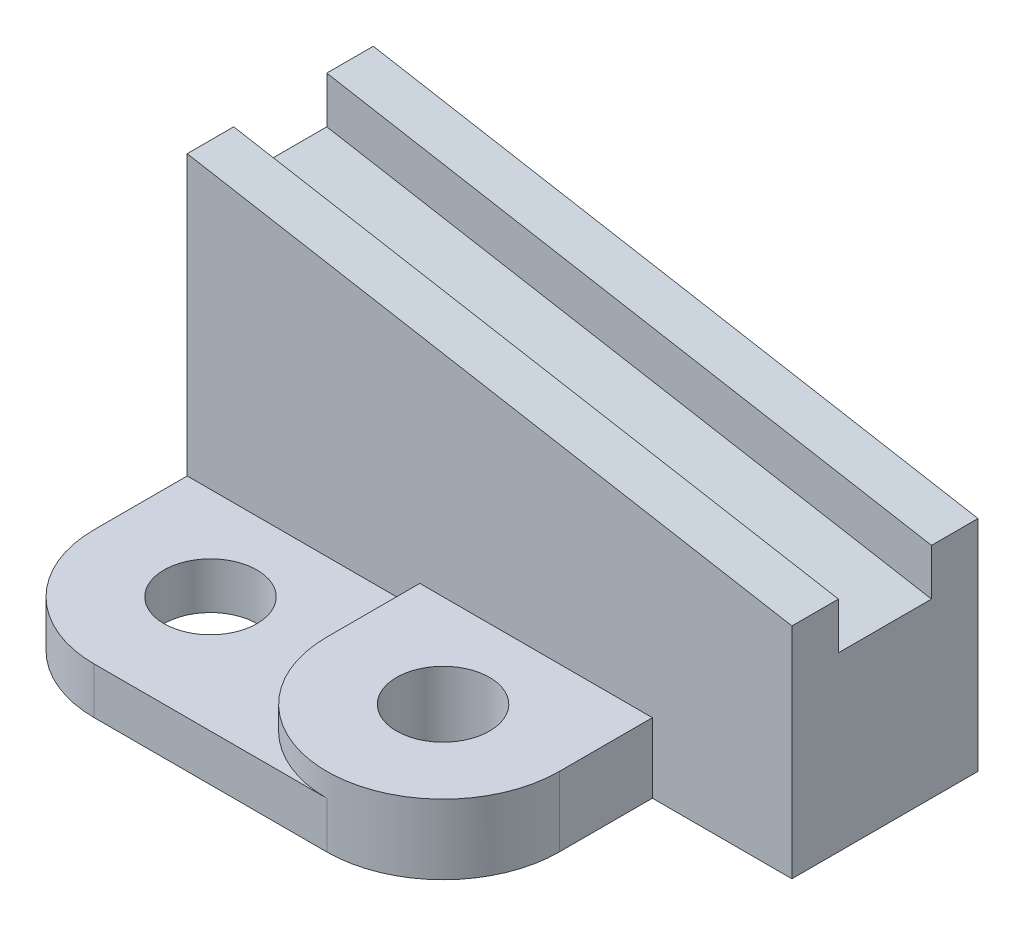
SolidWorks part; units mm, degrees
ref_plane "정면" through (0, 0, 0) normal (0, 0, 1) x (1, 0, 0)
ref_plane "윗면" through (0, 0, 0) normal (0, 1, 0) x (1, 0, 0)
ref_plane "우측면" through (0, 0, 0) normal (1, 0, 0) x (0, 0, -1)
sketch "스케치1" plane through (0, 0, 0) normal (0, 1, 0) x (1, 0, 0)
  line L0 (0, 0) -> (130, 0)
  line L1 (130, 0) -> (130, -10)
  line L2 (0, 0) -> (0, -10)
  line L3 (0, -10) -> (130, -10)
  line L4 (0, -10) -> (0, -30)
  line L5 (0, -30) -> (130, -30)
  line L6 (0, -30) -> (0, -40)
  line L7 (0, -40) -> (130, -40)
  line L8 (130, -10) -> (130, -30)
  line L9 (130, -40) -> (130, -30)
  line L10 (0, -40) -> (0, -60)
  line L11 (0, -60) -> (145.0013, -60) construction
  line L12 (100, -60) -> (100, -40)
  line L13 (25, -85) -> (75, -85)
  line L14 (25, -40) -> (25, -87.1847) construction
  line L15 (75, -40) -> (75, -87.1847) construction
  line L16 (50, -60) -> (50, -40)
  arc A0 (0, -60) -> (25, -85) centre (25, -60) ccw
  arc A1 (50, -60) -> (100, -60) centre (75, -60) ccw
  circle A2 centre (25, -60) radius 10
  circle A3 centre (75, -60) radius 10
  dimension "D6" = 25
  dimension "D7" = 50
  dimension "D1" = 20
  dimension "D2" = 10
  dimension "D3" = 10
  dimension "D4" = 130
  dimension "D5" = 20
extrude "보스-돌출1" add sketch "스케치1" along normal blind 70 contours L2 L3 L1 L0 | L7 L9 L5 L6 region at (65, 0, 5) region at (65, 0, 35)
extrude "보스-돌출2" add sketch "스케치1<3>" along normal blind 60 contours L8 L3 L4 L5 region at (65, 0, 20)
sketch "스케치1<3>" plane through (0, 0, 0) normal (0, 1, 0) x (1, 0, 0) same geometry as "스케치1"
sketch "스케치2" plane through (0, 0, 40) normal (0, 0, 1) x (1, 0, 0)
  line L0 (0, 70) -> (130, 47.0775)
  line L1 (130, 70) -> (130, 0) construction
  line L2 (130, 47.0775) -> (130, 70)
  line L3 (130, 70) -> (0, 70)
  line L4 (0, 70) -> (0, 60)
  line L5 (0, 60) -> (130, 37.0775)
  line L6 (130, 37.0775) -> (130, 70)
  line L7 (0, 70) -> (0, 60)
  line L8 (130, 70) -> (130, 0) construction
  line M5 (130, 0) -> (130, 70)
  line M6 (130, 70) -> (0, 70)
  dimension "D1" = 100
  dimension "D2" = 100
sketch "스케치3" plane through (130, 0, 0) normal (1, 0, 0) x (0, 0, -1)
  line L0 (-30, 60) -> (-30, 37.0775)
  line L1 (-30, 60) -> (-10, 60)
  line L2 (-10, 60) -> (-10, 37.0775)
  line L3 (-10, 37.0775) -> (-30, 37.0775)
  line M10 (-10, 60) -> (-30, 60)
extrude "컷-돌출4" cut sketch "스케치3" against normal blind 130 contours L3 L2 L0 M10 region at (130, 48.5387, 20)
extrude "컷-돌출5" cut sketch "스케치2" against normal through all and the other way through all contours L0 M6 M5 region at (86.6667, 62.3592, 40)
sketch "스케치4" plane through (0, 0, 40) normal (0, 0, 1) x (1, 0, 0)
  line L0 (130, 37.0775) -> (0, 37.0775)
  line L1 (0, 70) -> (0, 0) construction
  line L2 (0, 37.0775) -> (0, 60)
  line L3 (0, 60) -> (130, 37.0775)
extrude "보스-돌출3" add sketch "스케치4" against normal up to vertex (30 mm away) up to point (130, 37.0775, 10)
extrude "보스-돌출4" add sketch "스케치1<4>" along normal blind 10 contours A1 L16 L7 L10 A0 L13 A2 | A1 L12 L7 L16 A3 region at (25, 0, 40.8746) region at (75, 0, 40.6727)
sketch "스케치1<4>" plane through (0, 0, 0) normal (0, 1, 0) x (1, 0, 0) same geometry as "스케치1"
extrude "보스-돌출5" add sketch "스케치1<5>" along normal blind 15 contours A1 L12 L7 L16 A3 region at (75, 0, 40.6727)
sketch "스케치1<5>" plane through (0, 0, 0) normal (0, 1, 0) x (1, 0, 0) same geometry as "스케치1"
